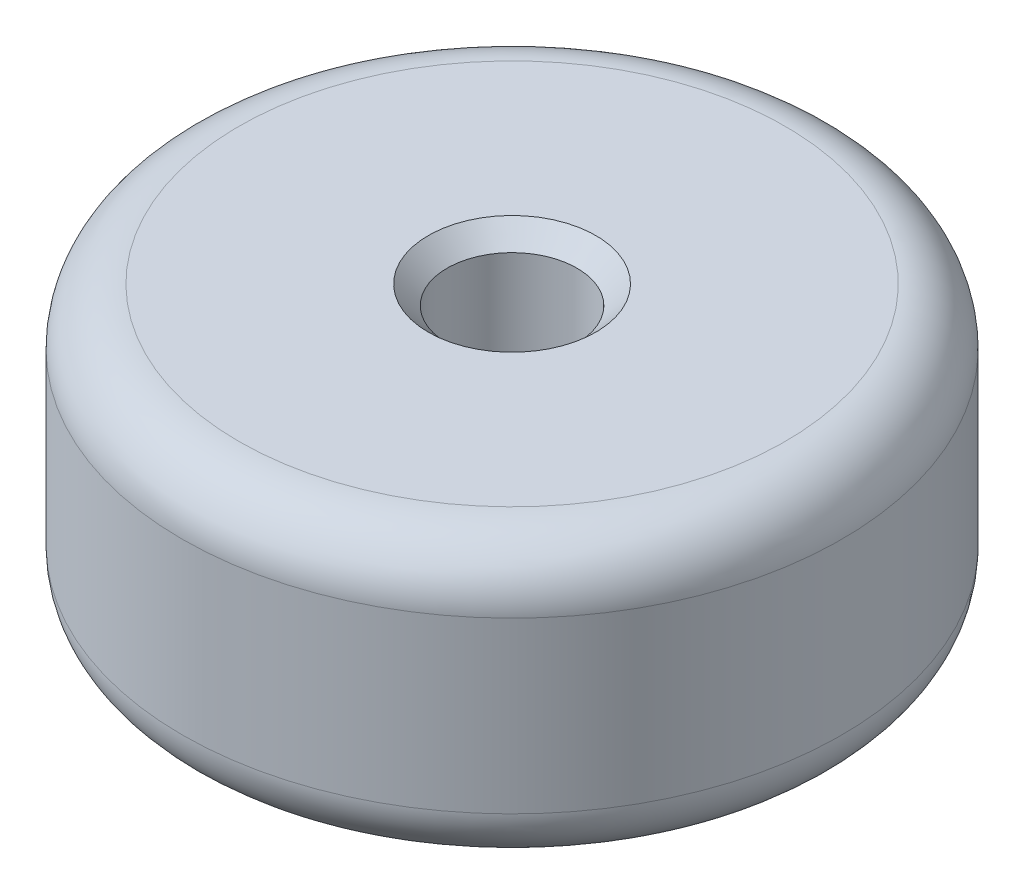
SolidWorks part; units mm, degrees
ref_plane "Front Plane" through (0, 0, 0) normal (0, 0, 1) x (1, 0, 0)
ref_plane "Top Plane" through (0, 0, 0) normal (0, 1, 0) x (1, 0, 0)
ref_plane "Right Plane" through (0, 0, 0) normal (1, 0, 0) x (0, 0, -1)
sketch "Sketch2" plane through (0, 0, 0) normal (0, 1, 0) x (1, 0, 0)
  circle A1 centre (0, 0) radius 17.5
  circle A2 centre (0, 0) radius 17.5
  dimension "D1" = 0
extrude "Boss-Extrude1" add sketch "Sketch2" along normal mid plane 15
fillet "Fillet1" radius 3 2 edges at (0, -7.5, 17.5) (0, 7.5, 17.5)
sketch "Sketch3" plane through (0, 0, 0) normal (0, 1, 0) x (1, 0, 0)
  circle A0 centre (0, 0) radius 5
  dimension "D1" = 10
extrude "Boss-Extrude2" [suppressed] add sketch "Sketch3" against normal offset from surface 0.25 and the other way offset from surface 0.25
sketch "Sketch4" plane through (0, 0, 0) normal (0, 1, 0) x (1, 0, 0)
  circle A0 centre (0, 0) radius 3.048 construction
  circle A1 centre (0, 0) radius 3.048 construction
  circle A2 centre (0, 0) radius 3.448
  dimension "D1" = 0.4
extrude "Cut-Extrude1" cut sketch "Sketch4" against normal through all both and the other way through all
sketch "Sketch5" plane through (0, 0, 0) normal (1, 0, 0) x (0, 0, -1)
  line L0 (-10.5, 7.5) -> (-12, 6)
  line L1 (14.5, 7.5) -> (-14.5, 7.5) construction
  line L2 (-12, 6) -> (-12, -6)
  line L3 (-12, -6) -> (-10.5, -7.5)
  line L4 (-14.5, -7.5) -> (14.5, -7.5) construction
  line L5 (-12, 0) -> (0, 0) construction
  line L6 (0, 0) -> (0, 3.4568) construction
  line L7 (-10.5, 7.5) -> (-17.9902, 7.5) construction
  dimension "D1" = 45
  dimension "D2" = 1.5
  dimension "D3" = 12
other "Cut-Revolve-Thin1" [suppressed] parameters "D1"=360, "D3"=0.1, "D4"=10, "D7"=0
chamfer "Chamfer1" distance 1 angle 45 2 edges at (0, 7.5, 3.448) (0, -7.5, 3.448)
fillet "Fillet2" [suppressed] radius 0.5
